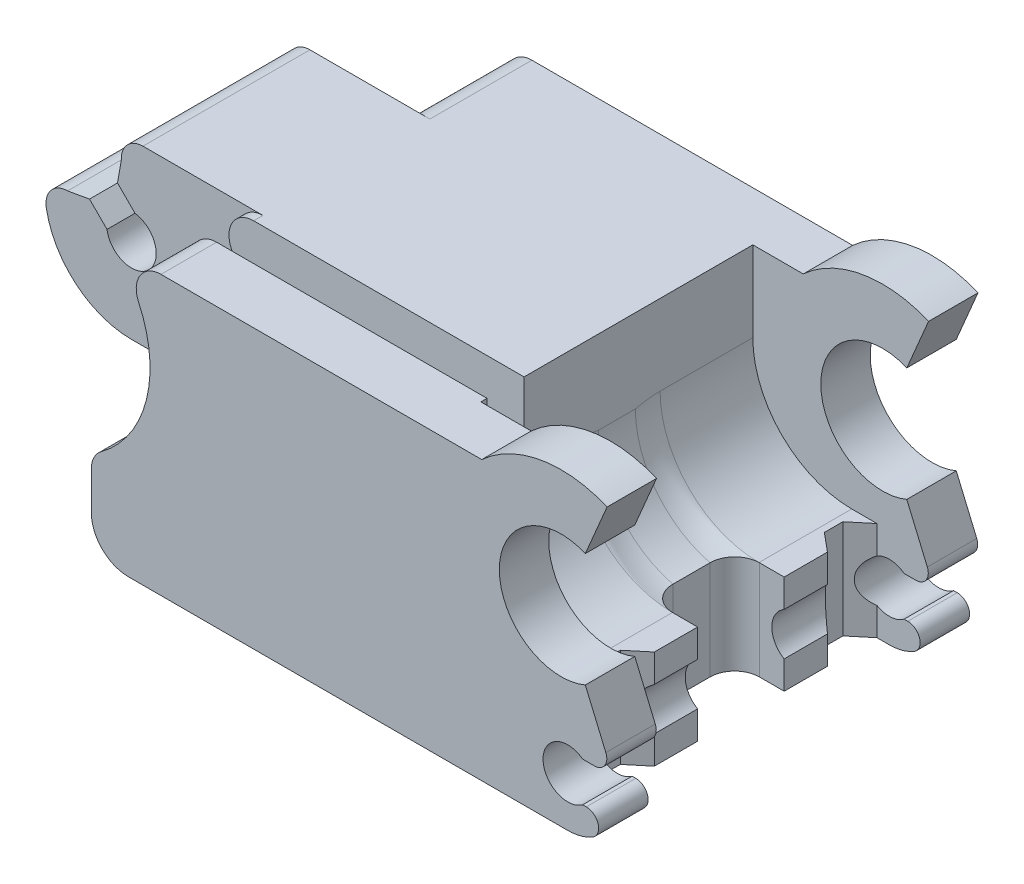
SolidWorks part; units mm, degrees
ref_plane "Front Plane" through (0, 0, 0) normal (0, 0, 1) x (1, 0, 0)
ref_plane "Top Plane" through (0, 0, 0) normal (0, 1, 0) x (1, 0, 0)
ref_plane "Right Plane" through (0, 0, 0) normal (1, 0, 0) x (0, 0, -1)
sketch "Sketch1" plane through (0, 0, 0) normal (0, 0, 1) x (1, 0, 0)
  line L0 (0, 0) -> (9.5, 0) construction
  line L1 (-52.5, 9.5) -> (9.5, 9.5)
  line L2 (-52.5, 9.5) -> (-52.5, -15.5)
  line L3 (-52.5, -15.5) -> (9.5, -15.5)
  line L4 (9.5, 9.5) -> (9.5, -15.5)
  line L5 (0, 0) -> (3.7119, 8.7448) construction
  line L6 (3.7119, 8.7448) -> (1.856, 4.3724)
  line L7 (3.7119, -8.7448) -> (1.856, -4.3724)
  line L8 (1.736, -9.9) -> (1.736, -13.1)
  line L9 (1.736, -9.9) -> (4.2021, -9.9)
  line L10 (1.736, -13.1) -> (4.2021, -13.1)
  line L11 (-42.7172, 1.9799) -> (-44.9799, -0.2828)
  line L12 (-52.5, -15.5) -> (-33, -15.5)
  line L13 (-52.5, -15.5) -> (-52.5, -6.5)
  line L16 (-42.7172, 1.9799) -> (-44.1314, 3.3941)
  line L17 (-48.1668, 0.8188) -> (-49.6208, 2.2728)
  line L18 (-43, 0) -> (-43.8485, 0.8485) construction
  line L19 (-46.3941, 1.1314) -> (-48.1668, 0.8188)
  line L20 (-43, 7) -> (-6.4226, 7)
  line L21 (-44.9799, -0.2828) -> (-46.3941, 1.1314)
  line L22 (-44.1314, 3.3941) -> (-43.8188, 5.1668)
  line L23 (-43.8188, 5.1668) -> (-45.2728, 6.6208)
  line L24 (-43, -7) -> (-33, -7)
  line L25 (-33, -7) -> (-33, -15.5)
  line L26 (4.2021, -9.9) -> (3.7119, -8.7448)
  line L27 (-33, -7) -> (-33, 0) construction
  line L28 (-38, -7) -> (-38, -15.5)
  line L29 (-43, 0) -> (-45, 0) construction
  circle A0 centre (0, 0) radius 2 construction
  circle A1 centre (-43, 0) radius 2
  circle A2 centre (0, 0) radius 5
  circle A3 centre (0, 0) radius 9.5
  circle A4 centre (0.536, -11.5) radius 2
  circle A5 centre (0.536, -11.5) radius 4
  circle A6 centre (-43, 0) radius 7
  circle A8 centre (-43, 0) radius 8.5 construction
  circle A9 centre (-43, 0) radius 9 construction
  point P39 (4.536, -11.5)
  dimension "D1" = 4
  dimension "D2" = 4
  dimension "D4" = 10
  dimension "D9" = 4
  dimension "D13" = 8
  dimension "D20" = 17
  dimension "D23" = 19
  dimension "D3" = 43
  dimension "D5" = 25
  dimension "D6" = 9.5
  dimension "D8" = 67
  dimension "D10" = 2
  dimension "D12" = 3.2
  dimension "D16" = 3.2
  dimension "D14" = 2
  dimension "D15" = 4.536
  dimension "D24" = 10
  dimension "D21" = 5
  dimension "D18" = 125
  dimension "D19" = 1.8
  dimension "D25" = 45
  dimension "D7" = 4.5
  dimension "D11" = 2
  dimension "D17" = 5
  dimension "D22" = 0.5
extrude "Boss-Extrude1" add sketch "Sketch1" along normal mid plane 30 contours A6 L23 L22 L16 A1 L21 L19 L17 | A6 L24 L25 L3 A5 A3 L20 | A5 A3 L7 A2 L6 | A3 A5 | L9 A5 A3 L10 A4 | A5 L26 A3 region at (1.8485, 9.0856, 0) region at (-21.1728, -4.3467, 0) region at (-38.1903, 4.8097, 0) region at (0.3999, -8.5786, 0) region at (0.4428, -9.4998, 0) region at (3.7778, -9.0652, 0)
fillet "Fillet1" radius 1 2 edges at (4.2021, -13.1, 0) (4.2021, -9.9, 0)
sketch "Sketch3" plane through (0, 0, 0) normal (0, 0, 1) x (1, 0, 0)
  line L0 (-33, -15.5) -> (0.536, -15.5) construction
  line L1 (-10.5, 10.2107) -> (7.5521, 10.2107)
  line L2 (-10.5, 10.2107) -> (-10.5, -15.5)
  line L3 (-10.5, -15.5) -> (7.5521, -15.5)
  line L4 (7.5521, 10.2107) -> (7.5521, -15.5)
  dimension "D1" = 10.5
extrude "Cut-Extrude1" cut sketch "Sketch3" against normal offset from surface 4 and the other way offset from surface 4 contours L4 L1 L2 L3 region at (-1.4739, -2.6446, 0) up to face at (-22.1936, -3.1826, -15) other way up to face at (-22.1936, -3.1826, 15)
sketch "Sketch5" plane through (0, 0, 15) normal (0, 0, 1) x (1, 0, 0)
  line L0 (-43, 7) -> (-6.4226, 7) construction
  line L1 (-33, -7) -> (-73.6432, -7)
  line L2 (-33, -7) -> (-33, 7)
  line L3 (-33, 7) -> (-73.6432, 7)
  line L4 (-73.6432, -7) -> (-73.6432, 7)
extrude "Cut-Extrude2" cut sketch "Sketch5" against normal offset from surface (8.25 mm away) 4.25 up to face at (-1.0933, -5.8791, 11) offset beyond the face yes
sketch "Sketch6" plane through (0, 0, -15) normal (0, 0, -1) x (-1, 0, 0)
  line L8 (33, -7) -> (73.6432, -7)
  line L9 (73.6432, -7) -> (73.6432, 7)
  line L10 (73.6432, 7) -> (33, 7)
  line L11 (33, 7) -> (33, -7)
  line L12 (33, -7) -> (73.6432, -7)
  line L13 (73.6432, -7) -> (73.6432, 7)
  line L14 (73.6432, 7) -> (33, 7)
  line L15 (33, 7) -> (33, -7)
  line M10 (33, -7) -> (43, -7)
  arc M11 (43, -7) -> (49.6208, 2.2728) centre (43, 0) ccw
  line M12 (49.6208, 2.2728) -> (48.1668, 0.8188)
  line M13 (48.1668, 0.8188) -> (46.3941, 1.1314)
  line M14 (46.3941, 1.1314) -> (44.9799, -0.2828)
  arc M15 (44.9799, -0.2828) -> (42.7172, 1.9799) centre (43, 0) cw
  line M16 (42.7172, 1.9799) -> (44.1314, 3.3941)
  line M17 (44.1314, 3.3941) -> (43.8188, 5.1668)
  line M18 (43.8188, 5.1668) -> (45.2728, 6.6208)
  arc M19 (45.2728, 6.6208) -> (43, 7) centre (43, 0) ccw
  line M20 (43, 7) -> (6.4226, 7)
  dimension "D1" = 0
extrude "Cut-Extrude3" cut sketch "Sketch6" against normal offset from surface (8.25 mm away) 4.25 contours M10 M11 M12 M13 M14 M15 M16 M17 M18 M19 M20 region at (-39.9173, -0.455, -15) up to face at (-1.0933, -5.8791, -11) offset beyond the face yes
sketch "Sketch7" plane through (0, 0, 0) normal (0, 0, 1) x (1, 0, 0)
  line L9 (-45.2728, 6.6208) -> (-43.8188, 5.1668)
  line L10 (-45.2728, 6.6208) -> (-43.8188, 5.1668)
  line L11 (-43.8188, 5.1668) -> (-44.1314, 3.3941)
  line L12 (-43.8188, 5.1668) -> (-44.1314, 3.3941)
  line L13 (-44.1314, 3.3941) -> (-42.7172, 1.9799)
  line L14 (-44.1314, 3.3941) -> (-42.7172, 1.9799)
  line L15 (-33, 7) -> (-43, 7)
  line L16 (-33, -7) -> (-33, 7)
  line L17 (-44.9799, -0.2828) -> (-46.3941, 1.1314)
  line L25 (-33, -7) -> (-33, 7)
  line L27 (-44.9799, -0.2828) -> (-46.3941, 1.1314)
  line L28 (-46.3941, 1.1314) -> (-48.1668, 0.8188)
  line L29 (-46.3941, 1.1314) -> (-48.1668, 0.8188)
  line L30 (-48.1668, 0.8188) -> (-49.6208, 2.2728)
  line L31 (-48.1668, 0.8188) -> (-49.6208, 2.2728)
  line L32 (-33, 7) -> (-43, 7)
  line L34 (-43, -7) -> (-33, -7)
  line L37 (-43, -7) -> (-33, -7)
  arc A1 (-43, 7) -> (-45.2728, 6.6208) centre (-43, 0) ccw
  arc A5 (-43, 7) -> (-45.2728, 6.6208) centre (-43, 0) ccw
  arc A9 (-44.9799, -0.2828) -> (-42.7172, 1.9799) centre (-43, 0) ccw
  arc A10 (-44.9799, -0.2828) -> (-42.7172, 1.9799) centre (-43, 0) ccw
  arc A11 (-49.6208, 2.2728) -> (-43, -7) centre (-43, 0) ccw
  arc A12 (-49.6208, 2.2728) -> (-43, -7) centre (-43, 0) ccw
  dimension "D1" = 0
fillet "Fillet2" radius 1.75 2 edges at (-49.6208, 2.2728, 0) (-45.2728, 6.6208, 0)
sketch "Sketch8" [suppressed] plane through (0, 0, -4.25) normal (0, 0, 1) x (1, 0, 0)
  line L0 (-53, 7) -> (-43, 7)
  line L1 (-43, 7) -> (-43, -7)
  line L2 (-43, -7) -> (-53, -7)
  arc A0 (-54.9799, -0.2828) -> (-52.7172, 1.9799) centre (-53, 0) ccw construction
  arc A1 (-54.9799, -0.2828) -> (-52.7172, 1.9799) centre (-53, 0) ccw
  circle A2 centre (-53, 0) radius 6 construction
  circle A3 centre (-53, 0) radius 7
  dimension "D1" = 17
sketch "Sketch10" plane through (0, 0, 6.75) normal (0, 0, 1) x (1, 0, 0)
  line L1 (-38, -7) -> (-38, -15.5) construction
  line L2 (-38, -7) -> (-38, -15.5)
  line L3 (-33, 7) -> (-36.2131, 7)
  line L6 (-42.0708, 7) -> (-33, 7) construction
  line L7 (-33, 7) -> (-33, -15.5)
  line L8 (-33, -15.5) -> (-38, -15.5)
  arc A0 (3.7119, 8.7448) -> (-6.4226, 7) centre (0, 0) ccw construction
  arc A1 (-44.9799, -0.2828) -> (-42.7172, 1.9799) centre (-43, 0) ccw construction
  arc A2 (3.7119, 8.7448) -> (-6.4226, 7) centre (0, 0) ccw construction
  arc A3 (-44.9799, -0.2828) -> (-42.7172, 1.9799) centre (-43, 0) ccw construction
  circle A4 centre (-43, 0) radius 9.75
  line M9 (-43, -7) -> (-33, -7)
  line M10 (-33, -7) -> (-33, 7)
  line M11 (-33, 7) -> (-42.0708, 7)
  dimension "D1" = 9.5
  dimension "D2" = 19.5
extrude "Boss-Extrude3" add sketch "Sketch10" along normal up to surface (8.25 mm away) contours A4 M9 M10 M11 | A4 L2 L8 L7 M9 region at (-35.4396, -11.3712, 6.75) region at (-33.889, -3.8566, 6.75) up to face at (-4.5548, -5.8791, 15)
sketch "Sketch41" plane through (0, 0, -6.75) normal (0, 0, -1) x (-1, 0, 0)
  line L0 (33, 7) -> (36.2131, 7) construction
  line L1 (33, 7) -> (33, -15.5) construction
  line L2 (33, -15.5) -> (38, -15.5) construction
  line L3 (38, -7) -> (38, -15.5) construction
  line L4 (33, 7) -> (36.2131, 7)
  line L5 (33, 7) -> (33, -15.5)
  line L6 (33, -15.5) -> (38, -15.5)
  line L7 (38, -7) -> (38, -15.5)
  circle A1 centre (43, 0) radius 9.75
  circle A2 centre (43, 0) radius 9.75
  line M10 (42.0708, 7) -> (33, 7)
  line M11 (33, 7) -> (33, -7)
  line M12 (33, -7) -> (43, -7)
  dimension "D1" = 0
extrude "Boss-Extrude6" add sketch "Sketch41" along normal up to surface (8.25 mm away) contours A2 L5 L6 L7 M12 | A2 M10 M11 M12 region at (-34.6065, 6.8564, -6.75) region at (-35.4396, -11.3712, -6.75) up to face at (-4.5548, -5.8791, -15)
fillet "Fillet4" radius 2 4 edges at (-38, -8.3703, 10.875) (-36.2131, 7, 10.875) (-38, -8.3703, -10.875) (-36.2131, 7, -10.875)
ref_plane "Plane1" through (0, 0, 9) normal (0, 0, 1) x (1, 0, 0)
sketch "Sketch11" plane through (0, 0, 9) normal (0, 0, -1) x (-1, 0, 0)
  line L0 (41.593, 5.317) -> (1.407, -5.317)
  arc A0 (42.7172, 1.9799) -> (44.9799, -0.2828) centre (43, 0) ccw construction
  arc A1 (42.7172, 1.9799) -> (44.9799, -0.2828) centre (43, 0) ccw construction
  arc A2 (-1.9537, -4.6025) -> (-1.9537, 4.6025) centre (0, 0) ccw construction
  arc A3 (-1.9537, -4.6025) -> (-1.9537, 4.6025) centre (0, 0) ccw construction
  circle A4 centre (43, 0) radius 5 construction
  circle A5 centre (0, 0) radius 5 construction
  circle A6 centre (43, 0) radius 5.5 construction
  circle A7 centre (0, 0) radius 5.5 construction
  dimension "D3" = 0.5
sweep "Cut-Sweep1" cut path "Sketch11" circular profile diameter 3 parameters "D3"=3
fillet "Fillet6" radius 3 2 edges at (-38, -15.5, 10.875) (-38, -15.5, -10.875)
sketch "Sketch24" plane through (0, 0, 0) normal (0, 0, 1) x (1, 0, 0)
  line L0 (-35, -15.5) -> (0.536, -15.5) construction
  line L1 (-35, -15.5) -> (0.536, -15.5) construction
  line L6 (-24.5, -13.5) -> (-24.5, -15.5) construction
  line L7 (-11.5, -13.5) -> (-11.5, -15.5) construction
  line L8 (-31.5, -13.5) -> (-31.5, -15.5)
  line L9 (-18.5, -13.5) -> (-18.5, -15.5)
  line L10 (-31.5, -15.5) -> (-18.5, -15.5)
  line L11 (-24.5, -15.5) -> (-11.5, -15.5) construction
  line L12 (-25, -7) -> (-38, -7)
  line L13 (-38, -9.4373) -> (-38, -12.5) construction
  line L14 (-38, -7) -> (-38, -15.5)
  line L15 (-38, -15.5) -> (-18.5, -15.5)
  circle A0 centre (-18, -13.5) radius 2 construction
  arc A5 (-44.9799, -0.2828) -> (-42.7172, 1.9799) centre (-43, 0) ccw construction
  arc A6 (-44.9799, -0.2828) -> (-42.7172, 1.9799) centre (-43, 0) ccw construction
  circle A7 centre (-25, -13.5) radius 2 construction
  arc A8 (-11.5, -13.5) -> (-24.5, -13.5) centre (-18, -13.5) ccw construction
  arc A9 (-18.5, -13.5) -> (-31.5, -13.5) centre (-25, -13.5) ccw
  circle A10 centre (-18, -13.5) radius 2.2 construction
  circle A11 centre (-25, -13.5) radius 2.2
  dimension "D1" = 4
  dimension "D2" = 18
  dimension "D3" = 4.5
  dimension "D4" = 18
  dimension "D5" = 0.2
extrude "Cut-Extrude6" cut sketch "Sketch24" against normal mid plane 8.5 contours A10 L11 L7 A8 L6 | A11 L10 L9 A9 L8 | A9 L12 L14 L15 L8 region at (-29.4864, -9.0136, 0) region at (-34.0872, -10.8555, 0)
sketch "Sketch45" plane through (0, 0, 0) normal (0, 0, 1) x (1, 0, 0)
  line L0 (3.612, -8.5093) -> (1.9537, -4.6025) construction
  line L1 (3.612, -8.5093) -> (1.9537, -4.6025)
  arc A0 (1.736, -9.9) -> (1.736, -13.1) centre (0.536, -11.5) ccw construction
  arc A1 (1.736, -9.9) -> (1.736, -13.1) centre (0.536, -11.5) ccw
sketch "Sketch47" plane through (0, 7, 0) normal (0, 1, 0) x (1, 0, 0)
  line L0 (-10.5, -7.5) -> (-33.8103, -7.5) construction
  line L1 (-5.5113, -7.5) -> (-48.8713, -7.5)
  line L2 (-33.8103, -10.5) -> (-10.5, -10.5) construction
  line L3 (-48.8713, -10.5) -> (-5.5113, -10.5)
  line L4 (-48.8713, -10.5) -> (-48.8713, -7.5)
  line L5 (-5.5113, -7.5) -> (-5.5113, -10.5)
extrude "Cut-Extrude7" cut sketch "Sketch47" against normal up to surface (11.2309 mm away) up to face at (-33.874, 3.265, 9.2218)
sketch "Sketch50" plane through (0, 0, 11) normal (0, 0, -1) x (-1, 0, 0)
  line L0 (0.464, -13.2321) -> (0.464, -15.5)
  line L1 (10.5, -15.5) -> (-0.536, -15.5) construction
  line L2 (10.5, 7) -> (10.5, -15.5) construction
  line L3 (10.5, 7) -> (10.5, -15.5)
  line L4 (0.464, -15.5) -> (10.5, -15.5)
  line L5 (0.464, -9.7679) -> (0.464, -7.5)
  line L6 (0.464, -7.5) -> (10.5, -7.5)
  arc A0 (-1.736, -13.1) -> (-1.736, -9.9) centre (-0.536, -11.5) ccw construction
  arc A1 (-1.736, -13.1) -> (-1.736, -9.9) centre (-0.536, -11.5) ccw
  arc M11 (-1.736, -9.9) -> (-1.736, -13.1) centre (-0.536, -11.5) cw
  line M15 (-0.536, -15.5) -> (10.5, -15.5)
  line M16 (10.5, -15.5) -> (10.5, 7)
  dimension "D1" = 4
  dimension "D2" = 4
extrude "Boss-Extrude7" add sketch "Sketch50" along normal up to vertex contours L6 L5 L0 M11 M15 M16 region at (-5.6274, -11.5, 11) up to point (-10.5, -15.5, -11)
sketch "Sketch51" plane through (0, -15.5, 0) normal (0, -1, 0) x (1, 0, 0)
  line L0 (-0.464, -11) -> (-0.464, 11) construction
  line L1 (-0.464, -11) -> (-0.464, 11)
  line L2 (-1.964, 8.25) -> (-1.964, 9.75)
  line L3 (-1.964, 9.75) -> (-0.464, 11)
  line L4 (-1.964, 9) -> (-0.464, 9) construction
  line L5 (-1.964, 8.25) -> (-0.464, 7)
  line L6 (-0.464, 0) -> (-3.9441, 0) construction
  line L7 (-1.964, -8.25) -> (-0.464, -7)
  line L8 (-1.964, -8.25) -> (-1.964, -9.75)
  line L9 (-1.964, -9.75) -> (-0.464, -11)
  line L12 (-0.464, 3.5) -> (-0.464, -4)
  line L13 (-0.464, 3.5) -> (-4.464, 3.5)
  line L14 (-0.464, 3.5) -> (-0.464, -3.5)
  line L15 (-0.464, -3.5) -> (-4.464, -3.5)
  line L16 (-4.464, 3.5) -> (-4.464, -3.5)
  point P2 (-1.964, 9)
  point P6 (-1.964, 9)
  point P17 (-4.464, 0)
  line M26 (-0.464, -11) -> (-0.464, 11)
  dimension "D2" = 1.5
  dimension "D3" = 1.5
  dimension "D4" = 7
  dimension "D5" = 4
extrude "Cut-Extrude8" cut sketch "Sketch51" against normal up to surface (8 mm away) contours L2 L5 L1 L3 | L8 L9 L7 M26 | L13 L16 L15 L12 region at (-1.1003, -15.5, -9) region at (-1.1003, -15.5, 9) region at (-2.464, -15.5, 0) up to face at (-5.482, -7.5, 0)
fillet "Fillet10" radius 2 2 edges at (-4.464, -11.5, 3.5) (-4.464, -11.5, -3.5)
fillet "Fillet11" radius 8 1 edges at (-10.5, -7.5, 0)
equation "\"mainSnapAngle\"= 67deg"
equation "\"D8@Sketch1\"=\"mainSnapAngle\""
equation "\"jointDistance\"= 43mm"
equation "\"mountBearingOD\"= 10mm"
equation "\"D3@Sketch1\"=\"jointDistance\""
equation "\"D4@Sketch1\"=\"mountBearingOD\""
equation "\"shaftDiameter\"= 4mm"
equation "\"D12@Sketch1\"=\"shaftDiameter\"*0.8"
equation "\"D2@Sketch1\"=\"shaftDiameter\""
equation "\"D1@Sketch1\"=\"shaftDiameter\""
equation "\"D16@Sketch1\"=\"D2@Sketch1\"*0.8"
equation "\"UgrooveOD\"= 17mm"
equation "\"D20@Sketch1\"=\"UgrooveOD\""
equation "\"D1@Sketch8\"=\"UgrooveOD\""
equation "\"D24@Sketch1\"= \"D23@Sketch1\" / 2 + 0.5"
equation "\"D2@Sketch10\"=\"D1@Sketch10\"*2+0.5"
equation "\"grooveDiameter\"= 10mm"
equation "\"tendonDiameter\" = 1mm"
equation "\"D3@Sketch11\"=\"tendonDiameter\"/2"
equation "\"D1@Sketch11\"=\"grooveDiameter\""
equation "\"D1@Sketch3\"=\"UgrooveOD\"/2+2"
equation "\"D2@Sketch50\"=\"D1@Sketch50\""
equation "\"D2@Sketch51\"=\"tendonDiameter\" +0.5"
equation "\"D3@Sketch51\"=\"D2@Sketch51\""
